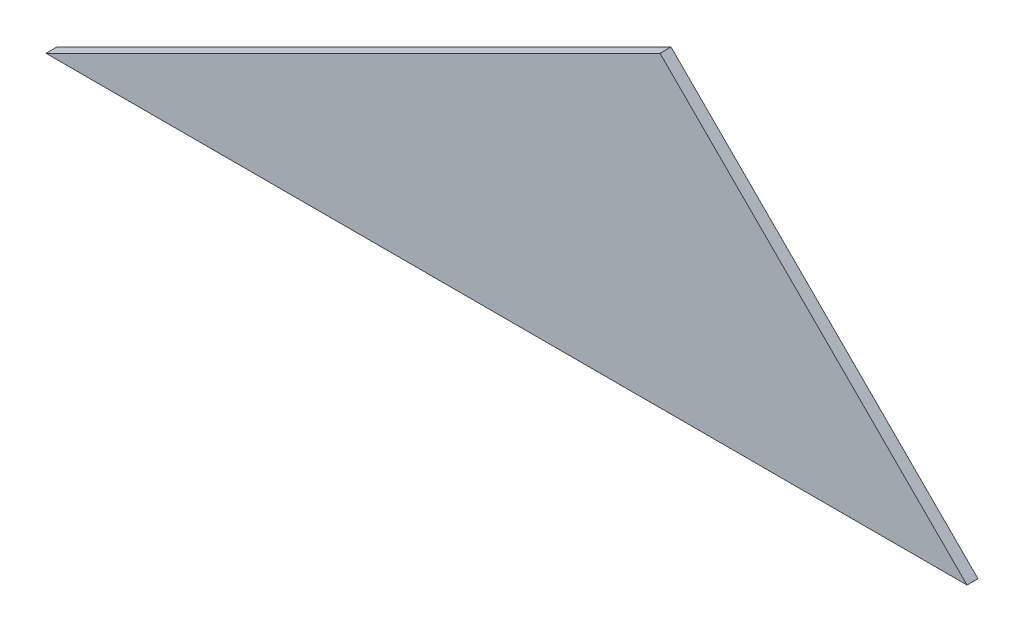
SolidWorks part; units mm, degrees
ref_plane "Front Plane" through (0, 0, 0) normal (0, 0, 1) x (1, 0, 0)
ref_plane "Top Plane" through (0, 0, 0) normal (0, 1, 0) x (1, 0, 0)
ref_plane "Right Plane" through (0, 0, 0) normal (1, 0, 0) x (0, 0, -1)
sketch "Sketch1" plane through (0, 0, 0) normal (0, 0, 1) x (1, 0, 0)
  line L0 (0, 0) -> (210, 0)
  line L1 (210, 0) -> (140, 70)
  line L2 (140, 70) -> (0, 0)
  dimension "D1" = 210
  dimension "D2" = 70
  dimension "D3" = 140
extrude "Boss-Extrude1" add sketch "Sketch1" along normal blind 2.5
ref_axis "Axis1" through (140, 70, 2.5) along (0, 0, -1)
ref_axis "Axis2" through (210, 0, 2.5) along (0, 0, -1)
